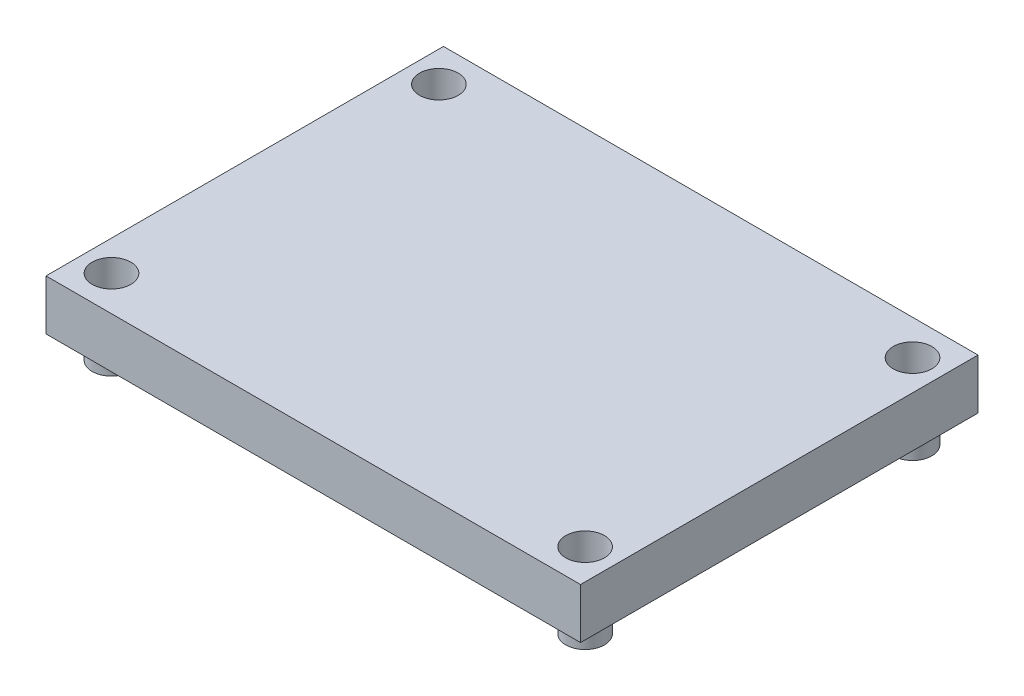
SolidWorks part; units mm, degrees
ref_plane "Front Plane" through (0, 0, 0) normal (0, 0, 1) x (1, 0, 0)
ref_plane "Top Plane" through (0, 0, 0) normal (0, 1, 0) x (1, 0, 0)
ref_plane "Right Plane" through (0, 0, 0) normal (1, 0, 0) x (0, 0, -1)
sketch "Sketch1" plane through (0, 0, 0) normal (0, 1, 0) x (1, 0, 0)
  line L1 (0, 0) -> (70.2, 0)
  line L2 (0, 0) -> (0, -52.2)
  line L3 (0, -52.2) -> (70.2, -52.2)
  line L4 (70.2, 0) -> (70.2, -52.2)
  circle A0 centre (4, -4.6) radius 2.54
  circle A1 centre (66.2, -4.6) radius 2.54
  circle A2 centre (66.2, -47.6) radius 2.54
  circle A3 centre (4, -47.6) radius 2.54
  point P13 (0, 0)
  point P14 (0, 0)
  point P15 (0, 0)
  point P16 (0, 0)
  point P17 (0, 0)
  point P18 (0, 0)
  dimension "D3" = 5.08
  dimension "D1" = 70.2
  dimension "D2" = 52.2
  dimension "D4" = 4.6
  dimension "D5" = 4
  dimension "D6" = 4.6
  dimension "D7" = 4
extrude "Boss-Extrude1" add sketch "Sketch1" along normal blind 6.604
extrude "Boss-Extrude2" add sketch "Sketch1<2>" against normal blind 3.302 separate body contours A1 | A2 | A3 | A0 region at (4, 0, 4.6) region at (66.2, 0, 4.6) region at (66.2, 0, 47.6) region at (4, 0, 47.6)
sketch "Sketch1<2>" plane through (0, 0, 0) normal (0, 1, 0) x (1, 0, 0) same geometry as "Sketch1"
equation "\"D6@Sketch1\"=\"D4@Sketch1\""
equation "\"D7@Sketch1\"=\"D5@Sketch1\""
